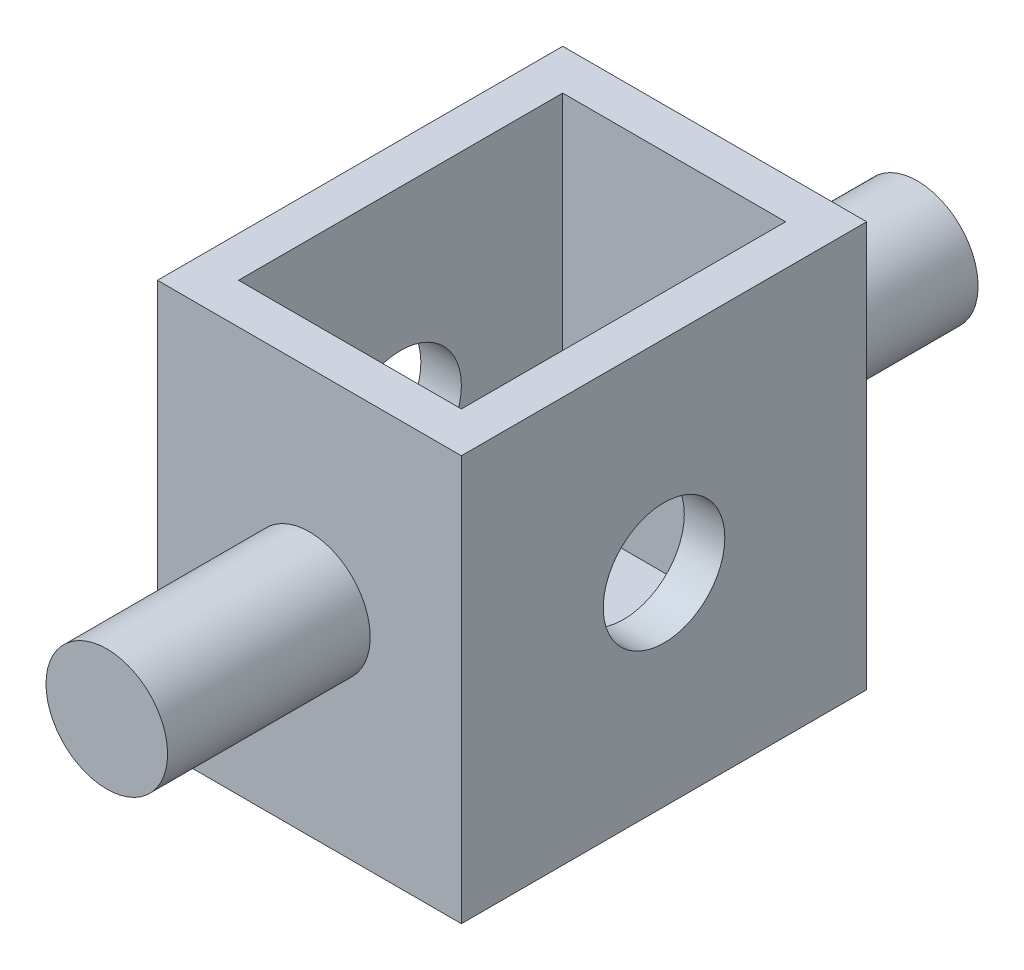
SolidWorks part; units mm, degrees
ref_plane "Front Plane" through (0, 0, 0) normal (0, 0, 1) x (1, 0, 0)
ref_plane "Top Plane" through (0, 0, 0) normal (0, 1, 0) x (1, 0, 0)
ref_plane "Right Plane" through (0, 0, 0) normal (1, 0, 0) x (0, 0, -1)
sketch "Sketch1" plane through (0, 0, 0) normal (0, 0, 1) x (1, 0, 0)
  line L1 (-9.525, -12.7) -> (9.525, -12.7)
  line L2 (-9.525, -12.7) -> (-9.525, 12.7)
  line L3 (-9.525, 12.7) -> (9.525, 12.7)
  line L4 (9.525, -12.7) -> (9.525, 12.7)
  line L5 (-9.525, -12.7) -> (9.525, 12.7) construction
  line L6 (-9.525, 12.7) -> (9.525, -12.7) construction
  point P0 (0, 0)
  dimension "D1" = 19.05
  dimension "D2" = 25.4
extrude "main body" add sketch "Sketch1" along normal blind 25.4
shell "hollow it" thickness 2.54 removed face at (0, 12.7, 12.7)
ref_point "cut point"
sketch "Sketch2" plane through (9.525, 0, 0) normal (1, 0, 0) x (0, 0, -1)
  circle A0 centre (-12.7, 0) radius 3.81
  dimension "D1" = 0
  dimension "D2" = 12.7
ref_point "bigger nibble point"
ref_point "bigger nibble here, too"
sketch "Sketch3" plane through (0, 0, 25.4) normal (0, 0, 1) x (1, 0, 0)
  circle A0 centre (0, 0) radius 3.81
  dimension "D1" = 7.62
extrude "nibble no 1" add sketch "Sketch3" along normal blind 12.7
sketch "Sketch4" plane through (0, 0, 0) normal (0, 0, -1) x (-1, 0, 0)
  circle A0 centre (0, 0) radius 3.81
  dimension "D1" = 7.62
extrude "nibble no 2" add sketch "Sketch4" along normal blind 12.7
ref_point "nibble center"
ref_plane "nibble flag plane" through (0, 0, 0) normal (0, -1, 0) x (-1, 0, 0)
sketch "Sketch5" plane through (0, 0, 0) normal (0, -1, 0) x (-1, 0, 0)
  line L1 (-0.8217, 4.4483) -> (0.4483, 4.4483)
  line L2 (-0.8217, 4.4483) -> (-0.8217, 8.2583)
  line L3 (-0.8217, 8.2583) -> (0.4483, 8.2583)
  line L4 (0.4483, 4.4483) -> (0.4483, 8.2583)
  line L5 (-0.8217, 4.4483) -> (0.4483, 8.2583) construction
  line L6 (-0.8217, 8.2583) -> (0.4483, 4.4483) construction
  point P0 (-0.1867, 6.3533)
  dimension "D1" = 1.27
  dimension "D2" = 3.81
extrude "flag" add sketch "Sketch5" along normal blind 0.254
extrude "nibble holes" cut sketch "Sketch2" against normal through all
